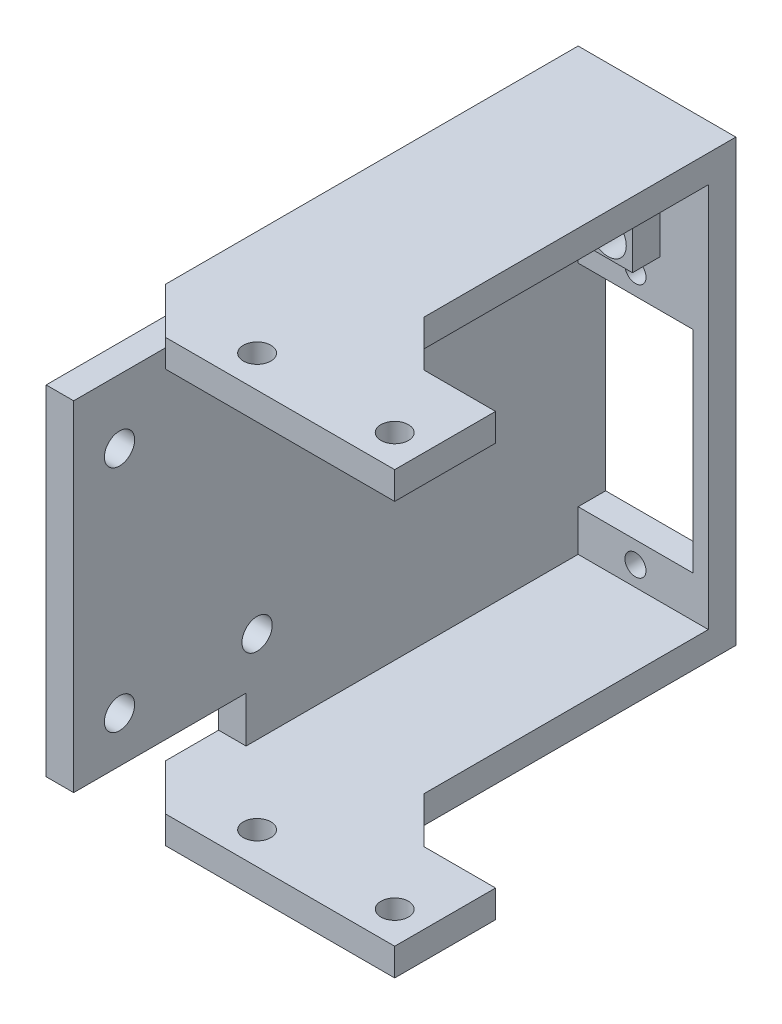
SolidWorks part; units mm, degrees
ref_plane "前视基准面" through (0, 0, 0) normal (0, 0, 1) x (1, 0, 0)
ref_plane "上视基准面" through (0, 0, 0) normal (0, 1, 0) x (1, 0, 0)
ref_plane "右视基准面" through (0, 0, 0) normal (1, 0, 0) x (0, 0, -1)
other "Configuration Table"
sketch "草图1" plane through (0, 0, 0) normal (0, 0, 1) x (1, 0, 0)
  line L1 (0, 0) -> (30, 0)
  line L2 (0, 0) -> (0, 48)
  line L3 (0, 48) -> (30, 48)
  line L4 (30, 0) -> (30, 48)
  dimension "D1" = 48
  dimension "D2" = 30
extrude "凸台-拉伸1" add sketch "草图1" along normal blind 3
sketch "草图3" plane through (0, 0, 3) normal (0, 0, 1) x (1, 0, 0)
  line L0 (30, 0) -> (30, 48) construction
  line L1 (0, 48) -> (30, 48)
  line L2 (0, 48) -> (0, 45)
  line L3 (0, 45) -> (30, 45)
  line L4 (30, 48) -> (30, 45)
  line L6 (0, 0) -> (30, 0)
  line L7 (0, 0) -> (0, 3)
  line L8 (0, 3) -> (30, 3)
  line L9 (30, 0) -> (30, 3)
  dimension "D1" = 3
  dimension "D2" = 3
extrude "凸台-拉伸2" add sketch "草图3" along normal blind 47
sketch "草图4" plane through (0, 0, 0) normal (0, 0, -1) x (-1, 0, 0)
  line L0 (0, 48) -> (0, 0) construction
  circle A1 centre (-9.25, 37.75) radius 2
  dimension "D1" = 4
  dimension "D2" = 9.25
sketch "草图5" plane through (0, 0, 0) normal (0, -1, 0) x (1, 0, 0)
  line L0 (0, 45) -> (5, 50)
  line L1 (0, 50) -> (0, 0) construction
  line L2 (0, 50) -> (30, 50) construction
  line L3 (5, 50) -> (0, 50)
  line L4 (0, 50) -> (0, 45)
  dimension "D1" = 45
  dimension "D2" = 5
extrude "切除-拉伸2" cut sketch "草图5" against normal through all
sketch "草图6" plane through (0, 0, 0) normal (0, -1, 0) x (1, 0, 0)
  line L0 (20, 0) -> (30, 10)
  line L1 (0, 0) -> (30, 0) construction
  line L2 (30, 50) -> (30, 0) construction
  line L3 (30, 10) -> (30, 0)
  line L4 (30, 0) -> (20, 0)
  dimension "D1" = 45
  dimension "D2" = 10
extrude "切除-拉伸3" cut sketch "草图6" against normal through all
sketch "草图7" plane through (0, 0, 3) normal (0, 0, 1) x (1, 0, 0)
  line L1 (0, 3) -> (3, 3)
  line L2 (0, 3) -> (0, 45)
  line L3 (0, 45) -> (3, 45)
  line L4 (3, 3) -> (3, 45)
  line L6 (5, 45) -> (0, 45) construction
extrude "凸台-拉伸3" add sketch "草图7" along normal blind 25
sketch "草图10" plane through (0, 0, 3) normal (0, 0, 1) x (1, 0, 0)
  line L0 (5, 45) -> (30, 45) construction
  line L1 (20.5, 12.8) -> (16.5, 12.8)
  line L2 (20.5, 12.8) -> (20.5, 45)
  line L3 (20.5, 45) -> (16.5, 45)
  line L4 (16.5, 12.8) -> (16.5, 45)
  dimension "D1" = 4
sketch "草图12" plane through (3, 0, 0) normal (1, 0, 0) x (0, 0, -1)
  line L1 (-23.1624, 31.4269) -> (-9.1105, 31.4269)
  line L2 (-23.1624, 31.4269) -> (-23.1624, 41.7502)
  line L3 (-23.1624, 41.7502) -> (-9.1105, 41.7502)
  line L4 (-9.1105, 31.4269) -> (-9.1105, 41.7502)
sketch "草图14" plane through (0, 0, 28) normal (0, 0, 1) x (1, 0, 0)
  line L4 (0, 45) -> (0, 3)
  line L5 (0, 3) -> (3, 3)
  line L6 (3, 3) -> (3, 45)
  line L7 (3, 45) -> (0, 45)
  line L8 (0, 45) -> (0, 3)
  line L10 (3, 3) -> (3, 45)
  line L11 (3, 45) -> (0, 45)
  line L12 (0, 3) -> (3, 3)
  dimension "D1" = 0
extrude "凸台-拉伸6" add sketch "草图14" along normal blind 30
sketch "草图15" plane through (0, 0, 0) normal (-1, 0, 0) x (0, 0, 1)
  circle A0 centre (38, 13) radius 1.65
  circle A1 centre (38, 38) radius 1.65
  circle A2 centre (53, 38) radius 1.65
  circle A3 centre (53, 13) radius 1.65
extrude "切除-拉伸6" cut sketch "草图15" against normal blind 4
sketch "草图16" plane through (0, 0, 3) normal (0, 0, 1) x (1, 0, 0)
  line L0 (3, 3) -> (3, 45) construction
  line L1 (15.5, 7.5) -> (3, 7.5)
  line L2 (15.5, 7.5) -> (15.5, 30.5)
  line L3 (15.5, 30.5) -> (3, 30.5)
  line L4 (3, 7.5) -> (3, 30.5)
  line L5 (3, 30.5) -> (15.5, 30.5) construction
  circle A0 centre (9.25, 32.85) radius 1.15
  circle A1 centre (9.25, 5.15) radius 1.15
  dimension "D1" = 2.3
  dimension "D2" = 2.3
extrude "切除-拉伸7" cut sketch "草图16" against normal blind 10
sketch "草图17" plane through (0, 0, 0) normal (-1, 0, 0) x (0, 0, 1)
  line L1 (58, 3) -> (39.2, 3)
  line L2 (58, 3) -> (58, 8)
  line L3 (58, 8) -> (39.2, 8)
  line L4 (39.2, 3) -> (39.2, 8)
  point P6 (27.2, 3)
extrude "切除-拉伸8" cut sketch "草图17" against normal blind 10
sketch "草图18" plane through (0, 48, 0) normal (0, 1, 0) x (1, 0, 0)
  line L0 (0, 0) -> (0, 9)
  line L1 (0, 9) -> (20, 9)
  line L2 (20, 9) -> (20, 0)
  line L3 (20, 0) -> (17, 0)
  line L4 (20, 0) -> (0, 0) construction
  line L5 (17, 0) -> (17, 6)
  line L6 (17, 6) -> (3, 6)
  line L7 (3, 6) -> (3, 0)
  line L8 (3, 0) -> (0, 0)
  dimension "D1" = 3
  dimension "D2" = 3
  dimension "D3" = 9
  dimension "D4" = 3
sketch "草图19" plane through (0, 0, 0) normal (0, 0, -1) x (-1, 0, 0)
sketch "草图20" plane through (0, 0, 0) normal (0, -1, 0) x (1, 0, 0)
  line L0 (0, 45) -> (0, 0) construction
  line L1 (5, 50) -> (30, 50) construction
  circle A1 centre (26.5, 46.5) radius 1.5
  circle A3 centre (11.5, 46.5) radius 1.5
  point P8 (0, 0)
  dimension "D1" = 3
  dimension "D2" = 3
  dimension "D5" = 3.5
  dimension "D3" = 11.5
  dimension "D4" = 15
extrude "切除-拉伸11" cut sketch "草图20" against normal through all
sketch "草图22" plane through (0, 0, 0) normal (0, 0, -1) x (-1, 0, 0)
  line L0 (-9.25, 5.15) -> (-9.25, 53.4853) construction
  circle A0 centre (-9.25, 37.75) radius 2
  circle A1 centre (-9.25, 13.75) radius 2 construction
  dimension "D1" = 24
  dimension "D2" = 4
extrude "切除-拉伸12" cut sketch "草图22" against normal up to next
sketch "草图23" plane through (0, 0, 3) normal (0, 0, 1) x (1, 0, 0)
  line L1 (6.3738, 35.5569) -> (11.9282, 35.5569)
  line L2 (6.3738, 35.5569) -> (6.3738, 40.2313)
  line L3 (6.3738, 40.2313) -> (11.9282, 40.2313)
  line L4 (11.9282, 35.5569) -> (11.9282, 40.2313)
  circle A0 centre (9.25, 37.75) radius 2 construction
  circle A1 centre (9.25, 37.75) radius 2
extrude "凸台-拉伸9" add sketch "草图23" along normal blind 3
sketch "草图25" plane through (0, 0, 3) normal (0, 0, 1) x (1, 0, 0)
  line L0 (9.25, 37.75) -> (9.25, 25.75) construction
  dimension "D1" = 12
sketch "草图27" plane through (0, 48, 0) normal (0, 1, 0) x (1, 0, 0)
  line L1 (30, -50) -> (17, -50)
  line L2 (30, -50) -> (30, 6.1562)
  line L3 (30, 6.1562) -> (17, 6.1562)
  line L4 (17, -50) -> (17, 6.1562)
  point P5 (16.7961, 6.1562)
  dimension "D1" = 13
sketch "草图30" plane through (0, 48, 0) normal (0, 1, 0) x (1, 0, 0)
  line L1 (32.1967, 0) -> (17.1967, 0)
  line L2 (32.1967, 0) -> (32.1967, -39.0018)
  line L3 (32.1967, -39.0018) -> (17.1967, -39.0018)
  line L4 (17.1967, 0) -> (17.1967, -39.0018)
  point P4 (15.9985, -26.3311)
  point P5 (16.9608, -28.9219)
  point P6 (17.1967, -39.0018)
  dimension "D1" = 15
extrude "切除-拉伸15" cut sketch "草图30" against normal through all
chamfer "倒角1" distance 5 angle 45 2 edges at (17.1967, 46.5, 39.0018) (17.1967, 1.5, 39.0018)
